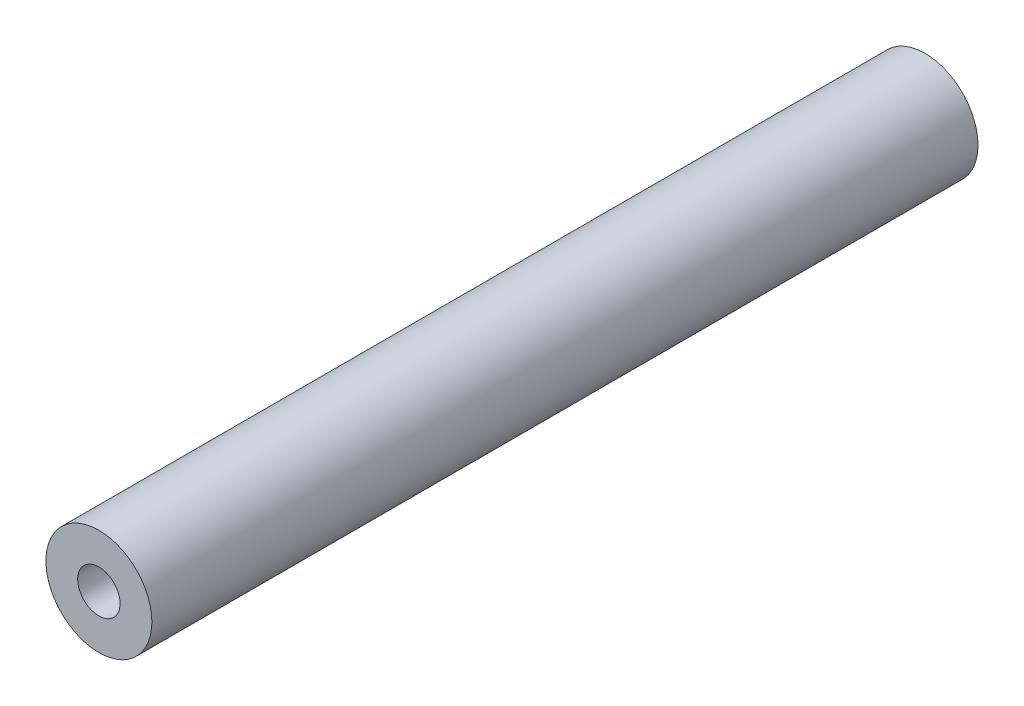
SolidWorks part; units mm, degrees
ref_plane "Alzado" through (0, 0, 0) normal (0, 0, 1) x (1, 0, 0)
ref_plane "Planta" through (0, 0, 0) normal (0, 1, 0) x (1, 0, 0)
ref_plane "Vista lateral" through (0, 0, 0) normal (1, 0, 0) x (0, 0, -1)
sketch "Croquis2" plane through (0, 0, 0) normal (0, 0, 1) x (1, 0, 0)
  circle A1 centre (0, 0) radius 5
  dimension "D2" = 10
extrude "Saliente-Extruir1" add sketch "Croquis2" along normal blind 77.95
sketch "Croquis3" plane through (0, 0, 77.95) normal (0, 0, 1) x (1, 0, 0)
  circle A0 centre (0, 0) radius 2.3813
  dimension "D1" = 4.7625
ref_plane "Plano1" through (0, 0, 31.125) normal (0, 0, 1) x (1, 0, 0)
sketch "Croquis4" plane through (0, 0, 77.95) normal (0, 0, 1) x (1, 0, 0)
  circle A0 centre (0, 0) radius 2
  dimension "D1" = 4
extrude "Cortar-Extruir1" cut sketch "Croquis4" against normal blind 10
sketch "Croquis5" plane through (0, 0, 0) normal (0, 0, -1) x (-1, 0, 0)
  circle A0 centre (0, 0) radius 2
  dimension "D1" = 4
extrude "Cortar-Extruir2" cut sketch "Croquis5" against normal blind 10
